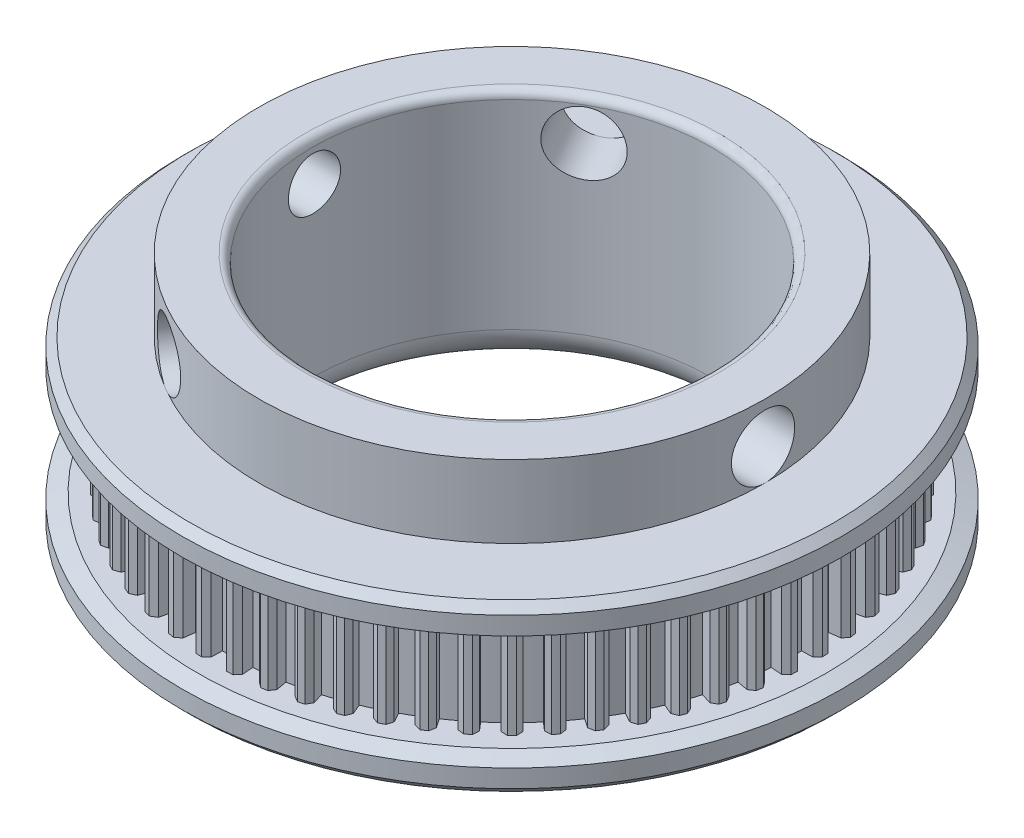
SolidWorks part; units mm, degrees
ref_plane "Plan de face" through (0, 0, 0) normal (0, 0, 1) x (1, 0, 0)
ref_plane "Plan de dessus" through (0, 0, 0) normal (0, 1, 0) x (1, 0, 0)
ref_plane "Plan de droite" through (0, 0, 0) normal (1, 0, 0) x (0, 0, -1)
sketch "Esquisse1" plane through (0, 0, 0) normal (0, 0, 1) x (1, 0, 0)
  line L0 (-12.6, -54.55) -> (-20.85, -54.55)
  line L1 (-20.85, -54.55) -> (-20.85, -52.914)
  line L2 (-20.85, -52.914) -> (-19.85, -52.55)
  line L3 (-19.85, -52.55) -> (-18.85, -52.55)
  line L4 (-18.85, -52.55) -> (-18.85, -46.05)
  line L5 (-18.85, -46.05) -> (-19.85, -46.05)
  line L6 (-19.85, -46.05) -> (-20.85, -45.686)
  line L7 (-20.85, -45.686) -> (-20.85, -44.05)
  line L8 (-20.85, -44.05) -> (-16, -44.05)
  line L9 (-16, -44.05) -> (-16, -39.45)
  line L10 (-16, -39.45) -> (-12.6, -39.45)
  line L11 (-12.6, -39.45) -> (-12.6, -54.55)
  line L12 (0, -59.8226) -> (0, -19) construction
  dimension "D2" = 18.85
  dimension "D3" = 2
  dimension "D4" = 160
  dimension "D5" = 160
  dimension "D6" = 1
  dimension "D7" = 1
  dimension "D8" = 6.5
  dimension "D9" = 2
  dimension "D10" = 2
  dimension "D11" = 4.6
revolve "Révolution1" add sketch "Esquisse1" angle 360 about L12
chamfer "Chanfrein1" distance 0.5 angle 45 2 edges at (20.85, -54.55, 0) (20.85, -44.05, 0)
sketch "Esquisse2" plane through (0, -46.05, 0) normal (0, -1, 0) x (1, 0, 0)
  line L0 (0, 0) -> (0, 18.95) construction
  line L1 (0, 0) -> (-1.9808, 18.8462) construction
  line L2 (-0.4961, 18.9435) -> (0, 0) construction
  line L3 (0, 0) -> (-1.4868, 18.8916) construction
  line L4 (-0.4673, 17.8439) -> (-0.4856, 18.5436)
  line L6 (-1.4554, 18.4928) -> (-1.4005, 17.795)
  line L9 (0, 17.85) -> (0, 18.95)
  line L10 (-1.9808, 18.8462) -> (-1.8658, 17.7522)
  line L11 (-0.7909, 18.8334) -> (-0.4856, 18.5436)
  line L12 (-1.182, 18.8129) -> (-1.4554, 18.4928)
  arc A0 (-0.4856, 18.5436) -> (-1.4554, 18.4928) centre (0, 0) ccw construction
  arc A2 (-0.4673, 17.8439) -> (-1.4005, 17.795) centre (0, 0) ccw construction
  arc A4 (0, 17.85) -> (-0.4673, 17.8439) centre (0, 0) ccw
  arc A5 (-1.4005, 17.795) -> (-1.8658, 17.7522) centre (0, 0) ccw
  arc A8 (0, 18.95) -> (-1.9808, 18.8462) centre (0, 0) ccw
  circle A9 centre (0, 0) radius 20.35 construction
  arc A10 (-0.7909, 18.8334) -> (-1.182, 18.8129) centre (0, 0) ccw
  dimension "D1" = 6
  dimension "D4" = 1
  dimension "D5" = 0.1
  dimension "D6" = 45
  dimension "D8" = 0.3
  dimension "D9" = 18.85
  dimension "D2" = 1.5
  dimension "D3" = 1.5
  dimension "D7" = 45
extrude "Enlèv. mat.-Extru.1" cut sketch "Esquisse2" along normal up to surface (6.5 mm away) up to face at (19.85, -52.55, 0)
pattern_circular "Répétition circulaire1" count 60 every 6 of "Enlèv. mat.-Extru.1"
sketch "Esquisse3" plane through (0, 0, 0) normal (1, 0, 0) x (0, 0, -1)
  line L0 (0, 0) -> (0, -41.95) construction
  line L1 (16, -44.05) -> (-16, -44.05) construction
  circle A0 centre (0, -41.95) radius 1.65
  dimension "D1" = 3.3
  dimension "D2" = 2.1
extrude "Enlèv. mat.-Extru.2" cut sketch "Esquisse3" against normal up to next
fillet "Congé1" radius 2 1 edges at (12.6, -54.55, 0)
sketch "Esquisse4" plane through (5.9767, -71.1, 0) normal (1, 0, 0) x (0, 0, 1)
  line L0 (0, -29.05) -> (0, -31.65) construction
  line L1 (-16, -31.65) -> (16, -31.65) construction
  line L2 (-16, -27.05) -> (16, -27.05) construction
  circle A0 centre (0, -29.05) radius 2
  dimension "D1" = 4
extrude "Enlèv. mat.-Extru.3" cut sketch "Esquisse4" along normal through all
pattern_circular "Répétition circulaire2" count 3 every 120 about axis through (0, -59.8226, 0) along (0, -1, 0) of "Enlèv. mat.-Extru.3" reverse direction yes
fillet "Congé2" radius 0.5 1 edges at (12.6, -39.45, 0)
